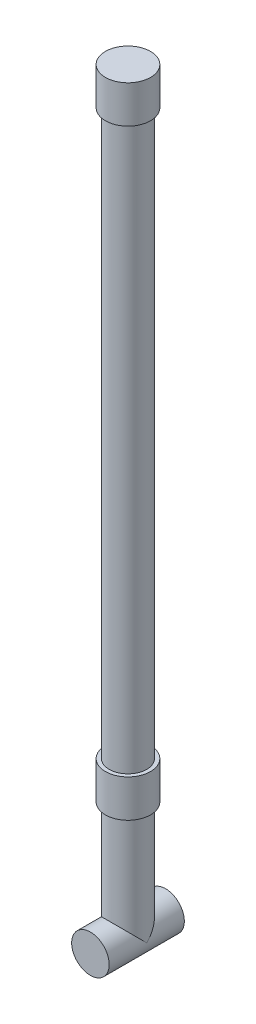
SolidWorks part; units mm, degrees
ref_plane "Front Plane" through (0, 0, 0) normal (0, 0, 1) x (1, 0, 0)
ref_plane "Top Plane" through (0, 0, 0) normal (0, 1, 0) x (1, 0, 0)
ref_plane "Right Plane" through (0, 0, 0) normal (1, 0, 0) x (0, 0, -1)
sketch "Sketch1" plane through (0, 0, 0) normal (0, 1, 0) x (1, 0, 0)
  circle A0 centre (0, 0) radius 5
  dimension "D1" = 10
extrude "Boss-Extrude1" add sketch "Sketch1" along normal blind 200
sketch "Sketch2" plane through (0, 0, 0) normal (0, 0, 1) x (1, 0, 0)
  circle A0 centre (0, 0) radius 5
extrude "Boss-Extrude2" add sketch "Sketch2" along normal blind 10 and the other way blind 10
sketch3d "3DSketch1"
  circle A0 centre (0, 30, 0) radius 6
  point P2 (0, 36, 0)
  dimension "D2" = 12
  dimension "D1" = 30
extrude "Boss-Extrude3" add sketch "3DSketch1" along direction (0, 1, 0) on the side of the normal blind 10
sketch "Sketch3" plane through (0, 200, 0) normal (0, 1, 0) x (1, 0, 0)
  circle A0 centre (0, 0) radius 6
  dimension "D1" = 12
extrude "Boss-Extrude4" add sketch "Sketch3" against normal blind 10
sketch3d "3DSketch2"
  line L0 (-5, 40, 0) -> (-5, 190, 0) construction
  circle A0 centre (0, 40, 0) radius 5 construction
  circle A1 centre (0, 190, 0) radius 5 construction
  point P4 (0, 45, 0)
  point P7 (0, 195, 0)
